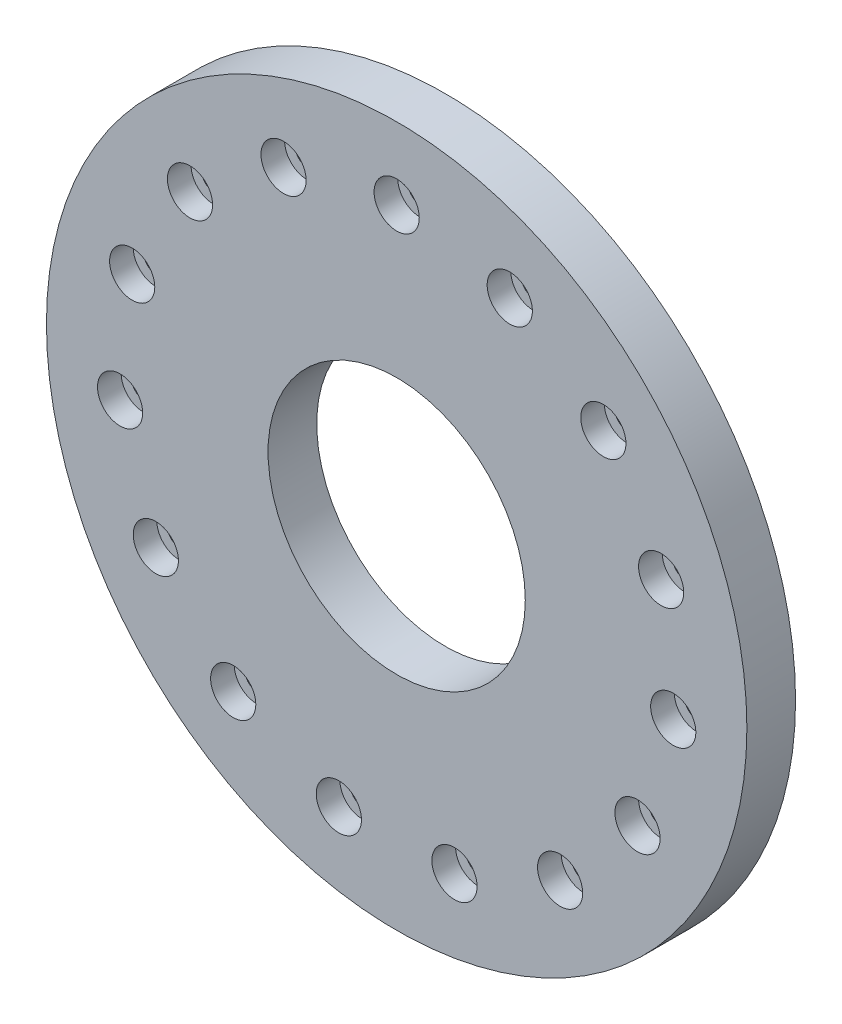
SolidWorks part; units mm, degrees
ref_plane "Front Plane" through (0, 0, 0) normal (0, 0, 1) x (1, 0, 0)
ref_plane "Top Plane" through (0, 0, 0) normal (0, 1, 0) x (1, 0, 0)
ref_plane "Right Plane" through (0, 0, 0) normal (1, 0, 0) x (0, 0, -1)
sketch "Sketch1" plane through (0, 0, 0) normal (0, 0, 1) x (1, 0, 0)
  circle A0 centre (0, 0) radius 50.375
  dimension "D1" = 100.75
extrude "Boss-Extrude1" add sketch "Sketch1" along normal blind 7 contours A0
sketch "Sketch2" plane through (0, 0, 7) normal (0, 0, 1) x (1, 0, 0)
  circle A0 centre (0, 40) radius 3
  circle A1 centre (16.2695, 36.5418) radius 3
  circle A2 centre (29.7258, 26.7652) radius 3
  circle A3 centre (38.0423, 12.3607) radius 3
  circle A4 centre (39.7809, -4.1811) radius 3
  circle A5 centre (34.641, -20) radius 3
  circle A6 centre (23.5114, -32.3607) radius 3
  circle A7 centre (8.3165, -39.1259) radius 3
  circle A8 centre (-8.3165, -39.1259) radius 3
  circle A9 centre (-23.5114, -32.3607) radius 3
  circle A10 centre (-34.641, -20) radius 3
  circle A11 centre (-39.7809, -4.1811) radius 3
  circle A12 centre (-38.0423, 12.3607) radius 3
  circle A13 centre (-29.7258, 26.7652) radius 3
  circle A14 centre (-16.2695, 36.5418) radius 3
  point P33 (0, 0)
  dimension "D2" = 6
  dimension "D1" = 40
  dimension "D3" = 15
extrude "Cut-Extrude1" [suppressed] cut sketch "Sketch2" against normal blind 5
sketch "Sketch3" plane through (0, 0, 7) normal (0, 0, 1) x (1, 0, 0)
  circle A0 centre (0, 0) radius 18.5
  dimension "D1" = 37
extrude "Cut-Extrude2" cut sketch "Sketch3" against normal through all
hole_wizard "CBORE for M3 Hex Socket Head Cap Screw1" positions "Sketch4" profile "Sketch6" counterbore size "M3" standard "ISO" end condition up to next
sketch "Sketch4" plane through (0, 0, 7) normal (0, 0, 1) x (1, 0, 0)
  point P0 (0, 40)
  dimension "D1" = 40
sketch "Sketch6" plane through (0, 40, 7) normal (1, 0, 0) x (0, -1, 0)
  line L0 (0, 0) -> (0, 7)
  line L1 (0, 7) -> (1.7, 7)
  line L3 (1.7, 7) -> (1.7, 3.4)
  line L4 (1.7, 3.4) -> (3.25, 3.4)
  line L5 (3.25, 3.4) -> (3.25, 0)
  line L7 (3.25, 0) -> (0, 0)
  line L11 (0, -6.35) -> (0, 107.95) construction
  dimension "Thru Hole Dia." = 3.4
  dimension "Thru Hole Depth" = 7
  dimension "C'Bore Dia." = 6.5
  dimension "C'Bore Depth" = 3.4
pattern_circular "CirPattern1" count 15 over 360 about axis through (0, 0, 7) along (0, 0, 1) of "CBORE for M3 Hex Socket Head Cap Screw1"
equation "\"roller_radius\"= 6.5"
equation "\"eccentricity\"= \"roller_radius\" * 0.325"
equation "\"outer_radius\"= 40"
equation "\"eccentric_shaft_radius\"= 16"
equation "\"rotor_width\"= 10"
equation "\"housing_depth\"= 40"
equation "\"bottom_depth\"= 5"
equation "\"roller_bearing_OD\"= \"roller_radius\" * 2"
equation "\"roller_bearing_ID\"= 6"
equation "\"eccentric_bearing_ID\"= 6"
equation "\"eccentric_bearing_OD\"= 15"
equation "\"roller_bearing_height\"= 5"
equation "\"eccentric_bearing_height\"= 5"
equation "\"bottom_bearing_ID\"= 15"
equation "\"bottom_bearing_OD\"= 32"
equation "\"bottom_bearing_height\"= 9"
equation "\"distance_to_output_rotor_holes\"= 20"
equation "\"D1@Sketch1\"=\"outer_radius\"*2+\"roller_bearing_OD\"*0.75+5.5*2"
equation "\"D1@Sketch2\"=\"outer_radius\""
equation "\"D2@Sketch2\"=\"roller_bearing_ID\""
equation "\"D1@Sketch3\"=\"output_bearing_OD\""
equation "\"D1@Sketch4\"=\"outer_radius\""
equation "\"output_bearing_ID\" = 25"
equation "\"output_bearing_OD\" = 37"
equation "\"output_bearing_height\" = 7"
equation "\"D1@Boss-Extrude1\"=\"output_bearing_height\""
